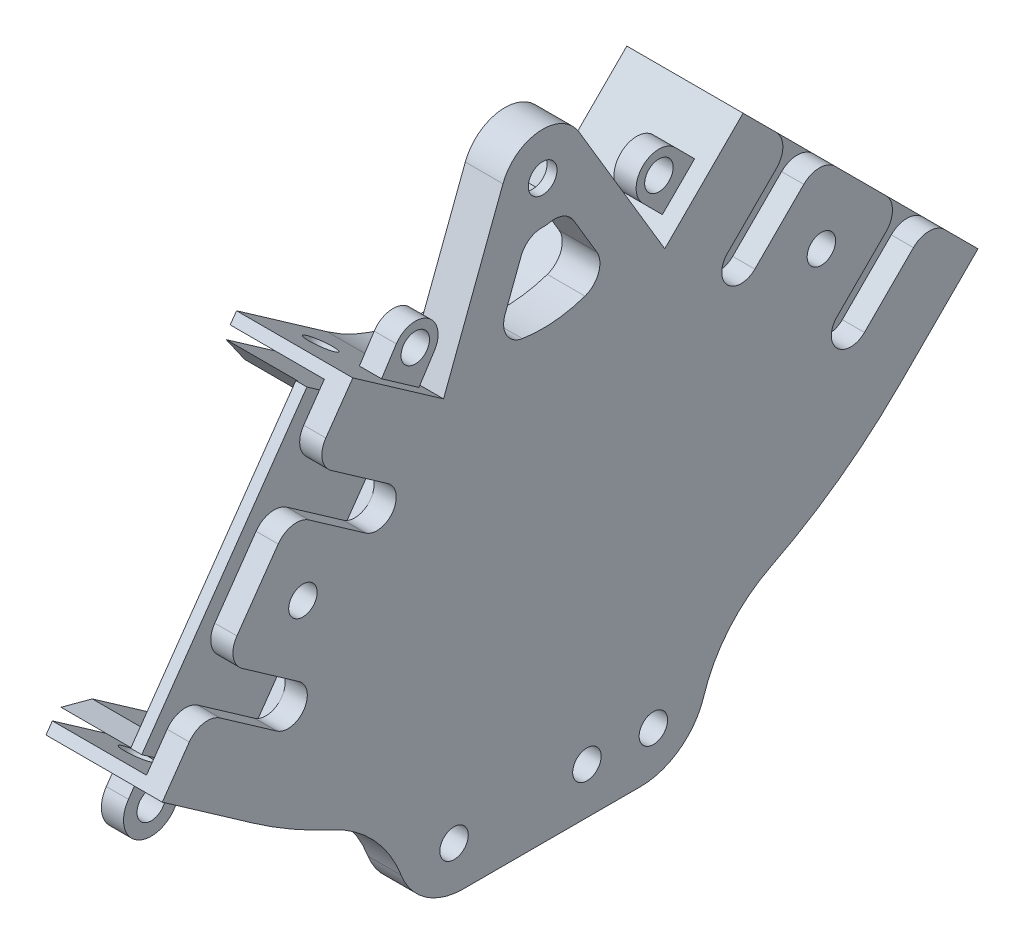
SolidWorks part; units mm, degrees
ref_plane "Front Plane" through (0, 0, 0) normal (0, 0, 1) x (1, 0, 0)
ref_plane "Top Plane" through (0, 0, 0) normal (0, 1, 0) x (1, 0, 0)
ref_plane "Right Plane" through (0, 0, 0) normal (1, 0, 0) x (0, 0, -1)
sketch "Sketch3" plane through (0, 0, 0) normal (1, 0, 0) x (0, 0, -1)
  line L0 (-22.7274, -32.4581) -> (-62.0633, -88.6355)
  line L1 (28.0184, -28.0184) -> (76.5118, -76.5118)
  line L2 (-22.7274, -32.4581) -> (0, 0) construction
  line L3 (0, 0) -> (28.0184, -28.0184) construction
  line L4 (0, 40.513) -> (0, -40.513) construction
  line L5 (-62.0633, -88.6355) -> (-66.4339, -94.8775)
  line L6 (76.5118, -76.5118) -> (81.8999, -81.8999)
  arc A2 (-62.0633, -88.6355) -> (76.5118, -76.5118) centre (0, 0) ccw
  arc A4 (-27.098, -38.7) -> (33.4066, -33.4066) centre (0, 0) ccw
  arc A5 (-22.7274, -32.4581) -> (28.0184, -28.0184) centre (0, 0) ccw
  arc A6 (-66.4339, -94.8775) -> (81.8999, -81.8999) centre (0, 0) ccw
  dimension "D1" = 216.408
  dimension "D2" = 135
  dimension "D3" = 94.488
  dimension "D4" = 7.62
  dimension "D6" = 7.62
  dimension "D5" = 80
extrude "Base extrude" add sketch "Sketch3" along normal blind 58.42 contours L5 A6 L6 A2 | A5 L0 A4 L1 region at (0, -39.9408, -3.4944) region at (0, -109.321, -9.5643)
sketch "Sketch4" plane through (58.42, 0, 0) normal (1, 0, 0) x (0, 0, -1)
  line L0 (-66.4339, -94.8775) -> (-22.7274, -32.4581)
  line L1 (28.0184, -28.0184) -> (81.8999, -81.8999)
  arc A0 (-22.7274, -32.4581) -> (28.0184, -28.0184) centre (0, 0) ccw
  arc A1 (-22.7274, -32.4581) -> (28.0184, -28.0184) centre (0, 0) ccw construction
  arc A2 (-66.4339, -94.8775) -> (81.8999, -81.8999) centre (0, 0) ccw
  arc A3 (-66.4339, -94.8775) -> (81.8999, -81.8999) centre (0, 0) ccw construction
  arc M1 (28.0184, -28.0184) -> (-22.7274, -32.4581) centre (0, 0) cw
  line M2 (-22.7274, -32.4581) -> (-27.098, -38.7)
  arc M3 (-27.098, -38.7) -> (33.4066, -33.4066) centre (0, 0) ccw
  line M4 (33.4066, -33.4066) -> (28.0184, -28.0184)
extrude "Outer wall" add sketch "Sketch4" along normal blind 7.62 contours L0 A2 L1 M3 | M4 M1 M2 M3 region at (58.42, -79.1939, -6.9286) region at (58.42, -39.9408, -3.4944)
ref_plane "Midplane" through (29.21, 0, 0) normal (-1, 0, 0) x (0, 0, 1)
mirror "Mirror1" about plane through (29.21, 0, 0) normal (-1, 0, 0) of "Outer wall"
sketch "Sketch6" plane through (0, 0, 0) normal (0, 0.5736, 0.8192) x (1, 0, 0)
  line L27 (-5.08, -42.164) -> (63.5, -42.164)
  line L28 (-5.08, -42.164) -> (-5.08, -113.284)
  line L29 (-5.08, -113.284) -> (63.5, -113.284)
  line L30 (63.5, -42.164) -> (63.5, -113.284)
  line L31 (-2.54, -44.704) -> (60.96, -44.704)
  line L32 (-2.54, -44.704) -> (-2.54, -110.744)
  line L33 (-2.54, -110.744) -> (60.96, -110.744)
  line L34 (60.96, -44.704) -> (60.96, -110.744)
  line L35 (58.42, -47.244) -> (0, -47.244) construction
  line L36 (0, -108.204) -> (0, -18.7894) construction
  line L37 (58.42, -18.7894) -> (58.42, -108.204) construction
  line L38 (58.42, -108.204) -> (0, -108.204) construction
  line L40 (0, -47.244) -> (58.42, -47.244)
  line L41 (0, -47.244) -> (0, -108.204)
  line L42 (0, -108.204) -> (58.42, -108.204)
  line L43 (58.42, -47.244) -> (58.42, -108.204)
  line L44 (-7.62, -39.624) -> (66.04, -39.624)
  line L45 (-7.62, -39.624) -> (-7.62, -115.824)
  line L46 (-7.62, -115.824) -> (66.04, -115.824)
  line L47 (66.04, -39.624) -> (66.04, -115.824)
  line M21 (-7.62, -39.624) -> (-7.62, -115.824)
  line M22 (-7.62, -115.824) -> (66.04, -115.824)
  line M23 (66.04, -115.824) -> (66.04, -39.624)
  line M24 (66.04, -39.624) -> (-7.62, -39.624)
  line M25 (58.42, -108.204) -> (0, -108.204)
  line M26 (0, -108.204) -> (0, -47.244)
  line M27 (0, -47.244) -> (58.42, -47.244)
  line M28 (58.42, -47.244) -> (58.42, -108.204)
  dimension "D1" = 2.54
  dimension "D2" = 2.54
  dimension "D3" = 2.54
  dimension "D4" = 2.54
  dimension "D5" = 2.54
  dimension "D6" = 2.54
  dimension "D7" = 2.54
  dimension "D8" = 2.54
extrude "Endcap 1" add sketch "Sketch6" along normal blind 25.4 contours L27 L30 L29 L28 M24 M21 M22 M23 | L34 L31 L32 L33 M28 M25 M26 M27 region at (29.21, -37.3698, 26.1667) region at (29.21, -33.3262, 23.3353)
sketch "Sketch7" plane through (0, 0, 0) normal (0, 0.7071, -0.7071) x (1, 0, 0)
  line L0 (-5.08, 113.284) -> (63.5, 113.284)
  line L1 (-5.08, 113.284) -> (-5.08, 42.164)
  line L2 (-5.08, 42.164) -> (63.5, 42.164)
  line L3 (63.5, 113.284) -> (63.5, 42.164)
  line L4 (-2.54, 110.744) -> (60.96, 110.744)
  line L5 (-2.54, 110.744) -> (-2.54, 44.704)
  line L6 (-2.54, 44.704) -> (60.96, 44.704)
  line L7 (60.96, 110.744) -> (60.96, 44.704)
  line L8 (0, 108.204) -> (58.42, 108.204)
  line L9 (0, 108.204) -> (0, 47.244)
  line L10 (0, 47.244) -> (58.42, 47.244)
  line L11 (58.42, 108.204) -> (58.42, 47.244)
  line L12 (-7.62, 115.824) -> (66.04, 115.824)
  line L13 (-7.62, 115.824) -> (-7.62, 39.624)
  line L14 (-7.62, 39.624) -> (66.04, 39.624)
  line L15 (66.04, 115.824) -> (66.04, 39.624)
  line L16 (58.42, 108.204) -> (0, 108.204) construction
  line L17 (58.42, 47.244) -> (58.42, 108.204) construction
  line L18 (66.04, 115.824) -> (-7.62, 115.824) construction
  line L19 (66.04, 39.624) -> (66.04, 115.824) construction
  line L20 (-7.62, 39.624) -> (-7.62, 115.824) construction
  line L21 (66.04, 39.624) -> (-7.62, 39.624) construction
  line M17 (66.04, 115.824) -> (-7.62, 115.824)
  line M18 (-7.62, 115.824) -> (-7.62, 39.624)
  line M19 (-7.62, 39.624) -> (66.04, 39.624)
  line M20 (66.04, 39.624) -> (66.04, 115.824)
  line M21 (0, 47.244) -> (0, 108.204)
  line M22 (0, 108.204) -> (58.42, 108.204)
  line M23 (58.42, 108.204) -> (58.42, 47.244)
  line M24 (58.42, 47.244) -> (0, 47.244)
  dimension "D1" = 2.54
  dimension "D2" = 2.54
  dimension "D3" = 2.54
  dimension "D4" = 2.54
  dimension "D5" = 2.54
  dimension "D6" = 2.54
  dimension "D7" = 2.54
  dimension "D8" = 2.54
extrude "Endcap 2" add sketch "Sketch7" along normal blind 25.4 contours L0 L3 L2 L1 M20 M17 M18 M19 | L7 L4 L5 L6 M24 M21 M22 M23 region at (29.21, -77.66, -77.66) region at (29.21, -81.1505, -81.1505)
chamfer "Internal Chamfer" distance 7.62 angle 20 4 edges at (29.21, -74.0667, 82.8697) (29.21, -24.1312, 47.9045) (29.21, -58.5513, -94.4723) (29.21, -15.446, -51.3671) first distance on face at (29.21, -81.3511, 72.4665) first distance on face at (29.21, -31.4156, 37.5013) first distance on face at (29.21, -67.5315, -85.492) first distance on face at (29.21, -24.4263, -42.3868)
ref_plane "Plane2" through (0, -13.9736, -1.2225) normal (0, -0.9962, -0.0872) x (-1, 0, 0)
sketch "Sketch10" plane through (0, -13.9736, -1.2225) normal (0, -0.9962, -0.0872) x (-1, 0, 0)
  line L0 (-66.04, 93.9078) -> (7.62, 93.9078) construction
  line L1 (-16.51, 95.5358) -> (-41.91, 95.5358)
  line L2 (-16.51, 95.5358) -> (-16.51, -82.1857)
  line L3 (-16.51, -82.1857) -> (-41.91, -82.1857)
  line L4 (-41.91, 95.5358) -> (-41.91, -82.1857)
  point P4 (-29.21, 93.9078)
  point P5 (-29.21, 95.5358)
  dimension "D1" = 25.4
extrude "Flywheel Hole" cut sketch "Sketch10" along normal up to next
sketch "Sketch11" plane through (-7.62, 0, 0) normal (-1, 0, 0) x (0, 0, 1)
  line L0 (-25.2982, 2.2719) -> (-28.0184, -28.0184)
  line L4 (-3.0636, -22.3183) -> (-4.5937, -39.3568)
  line L5 (6.8995, -21.445) -> (11.3704, -37.9575)
  line L6 (-20.4217, -1.79) -> (20.4217, 1.79) construction
  line L7 (24.5172, 6.6383) -> (33.1306, -25.1737)
  line L8 (43.5339, -17.8892) -> (22.7274, -32.4581) construction
  line L10 (1.5525, -17.7121) -> (-2.2178, 25.303) construction
  line L11 (22.7274, -32.4581) -> (43.5339, -17.8892)
  line L12 (22.7274, -32.4581) -> (33.1306, -25.1737)
  arc A1 (-28.0184, -28.0184) -> (22.7274, -32.4581) centre (0, 0) ccw construction
  circle A3 centre (0, 0) radius 4.064
  arc A4 (24.5172, 6.6383) -> (-25.2982, 2.2719) centre (0, 0) ccw
  circle A6 centre (-20.4217, -1.79) radius 2.5
  circle A7 centre (20.4217, 1.79) radius 2.5
  arc A8 (-3.0636, -22.3183) -> (6.8995, -21.445) centre (1.9961, -22.7727) cw
  arc A11 (11.3704, -37.9575) -> (22.7274, -32.4581) centre (0, 0) ccw
  arc A12 (-28.0184, -28.0184) -> (22.7274, -32.4581) centre (0, 0) ccw
  arc A13 (-28.0184, -28.0184) -> (-4.5937, -39.3568) centre (0, 0) ccw
  point P22 (0, 0)
  dimension "D3" = 8.128
  dimension "D2" = 25.4
  dimension "D1" = 5
  dimension "D5" = 5.08
  dimension "D4" = 41
  dimension "D7" = 43.18
  dimension "D6" = 0
extrude "Flywheel holder" add sketch "Sketch11" against normal blind 7.62
sketch "Sketch12" plane through (-7.62, 0, 0) normal (-1, 0, 0) x (0, 0, 1)
  circle A0 centre (0, 0) radius 14.605
  dimension "D1" = 29.21
extrude "Motor insert" cut sketch "Sketch12" against normal blind 6.35
sketch "Sketch14" plane through (-7.62, 0, 0) normal (-1, 0, 0) x (0, 0, 1)
  line L1 (-106.5763, 40.9543) -> (105.556, 40.9543)
  line L2 (-106.5763, 40.9543) -> (-106.5763, -120.0185)
  line L3 (-106.5763, -120.0185) -> (105.556, -120.0185)
  line L4 (105.556, 40.9543) -> (105.556, -120.0185)
extrude "Cut-Extrude2" cut sketch "Sketch14" against normal up to surface (49.53 mm away) up to face at (41.91, -26.9401, -2.3569)
sketch "Sketch15" plane through (41.91, 0, 0) normal (-1, 0, 0) x (0, 0, 1)
  line L0 (-93.8083, -77.7308) -> (-89.6212, -74.1787)
  line L1 (-99.8604, -63.9394) -> (-81.8999, -81.8999) construction
  line L2 (-89.6212, -74.1787) -> (-80.6312, -83.1493)
  line L3 (-80.6312, -83.1493) -> (-85.0539, -86.9012)
  line L4 (-16.51, -121.4959) -> (-16.51, -114.6413)
  line L5 (-16.51, -114.6413) -> (-3.8593, -115.7597)
  line L6 (-3.8593, -115.7597) -> (-3.8593, -120.7059)
  line L7 (63.1155, -104.8839) -> (59.3284, -99.4753)
  line L8 (59.3284, -99.4753) -> (69.9059, -92.4464)
  line L9 (66.4339, -94.8775) -> (87.2404, -80.3086) construction
  line L10 (69.9059, -92.4464) -> (73.4123, -97.454)
  circle A0 centre (-89.7004, -82.5731) radius 3.2639
  circle A1 centre (-10.16, -121.4959) radius 3.2639
  circle A2 centre (68.1904, -101.0671) radius 3.2639
  arc A3 (-93.8083, -77.7308) -> (-85.0539, -86.9012) centre (-89.7004, -82.5731) ccw
  arc A5 (62.868, -104.5305) -> (73.3715, -97.3959) centre (68.1904, -101.0671) ccw
  arc A6 (-81.8999, -81.8999) -> (66.4339, -94.8775) centre (0, 0) ccw construction
  arc A7 (-16.51, -121.4959) -> (-3.8593, -120.7059) centre (-10.16, -121.4959) ccw
  line M28 (-99.8604, -63.9394) -> (-81.8999, -81.8999)
  arc M29 (-81.8999, -81.8999) -> (66.4339, -94.8775) centre (0, 0) ccw
  line M30 (66.4339, -94.8775) -> (87.2404, -80.3086)
  dimension "D4" = 6.5278
  dimension "D5" = 12.7
  dimension "D1" = 121.92
  dimension "D2" = 121.92
  dimension "D3" = 121.92
  dimension "D6" = 10.16
  dimension "D7" = 10.16
  dimension "D8" = 19.05
  dimension "D9" = 12.7
  dimension "D10" = 12.7
  dimension "D11" = 12.7
extrude "Joining screw holes" add sketch "Sketch15" against normal blind 5.08 contours L0 A3 L3 A0 M29 M28 | L4 A7 L6 A1 M29 | L7 A5 L10 A2 M30 M29 region at (41.91, -97.4205, 63.0391) region at (41.91, -115.5565, -10.2161) region at (41.91, -76.1174, -91.5767)
ref_plane "Plane3" through (59.69, 0, 0) normal (1, 0, 0) x (0, 0, -1)
sketch "Sketch16" plane through (59.69, 0, 0) normal (1, 0, 0) x (0, 0, -1)
  line L0 (-43.5339, -17.8892) -> (-22.7274, -32.4581) construction
  line L1 (45.9789, -10.0579) -> (28.0184, -28.0184) construction
  line L2 (-29.7459, -19.9251) -> (-33.1306, -25.1737)
  line L3 (-33.1306, -25.1737) -> (-24.5641, -31.172)
  line L4 (-24.5641, -31.172) -> (-21.1794, -25.9235)
  line L5 (26.7818, -20.2747) -> (31.2719, -24.7649)
  line L6 (31.2719, -24.7649) -> (38.6683, -17.3685)
  line L7 (38.6683, -17.3685) -> (34.1782, -12.8783)
  line L8 (34.1782, -12.8783) -> (26.7818, -20.2747) construction
  circle A0 centre (-25.4, -22.8348) radius 3.2639
  circle A1 centre (30.48, -16.5765) radius 3.2639
  arc A2 (-21.1794, -25.9235) -> (-29.8435, -20.0764) centre (-25.4, -22.8348) ccw
  arc A3 (34.1782, -12.8783) -> (26.7818, -20.2747) centre (30.48, -16.5765) ccw
  dimension "D3" = 6.5278
  dimension "D1" = 6.35
  dimension "D2" = 6.35
  dimension "D4" = 25.4
  dimension "D5" = 30.48
  dimension "D6" = 55.88
  dimension "D7" = 6.2582
extrude "Flywheel cover connectors" add sketch "Sketch16" along normal blind 5.08 contours L4 A2 L2 L3 A0 | L7 L8 A1 L5 L6 | L8 A3 A1 region at (59.69, -18.7043, 22.5078) region at (59.69, -19.2478, -33.1513) region at (59.69, -12.9676, -26.8711)
sketch "Sketch17" plane through (66.04, 0, 0) normal (1, 0, 0) x (0, 0, -1)
  line L0 (-30.48, -111.7415) -> (-30.48, -132.08)
  line L1 (-30.48, -132.08) -> (35.56, -132.08)
  line L2 (35.56, -132.08) -> (35.56, -110.2301)
  circle A0 centre (-20.32, -121.92) radius 3.2639
  circle A1 centre (25.4, -121.92) radius 3.2639
  arc A2 (-66.4339, -94.8775) -> (81.8999, -81.8999) centre (0, 0) ccw construction
  circle A4 centre (10.16, -121.4959) radius 3.2639
  arc A5 (-66.4339, -94.8775) -> (81.8999, -81.8999) centre (0, 0) ccw
  arc A6 (-30.48, -111.7415) -> (35.56, -110.2301) centre (0, 0) ccw
  circle A7 centre (10.16, -121.4959) radius 3.2639 construction
  dimension "D1" = 6.5278
  dimension "D2" = 20.32
  dimension "D3" = 25.4
  dimension "D4" = 121.92
  dimension "D5" = 0
  dimension "D6" = 10.16
  dimension "D7" = 10.16
  dimension "D8" = 10.16
extrude "80-20 connector" add sketch "Sketch17" against normal blind 5.08
fillet "Fillet1" radius 30.48 2 edges at (63.5, -111.7415, 30.48) (63.5, -110.2301, -35.56)
fillet "Fillet2" radius 15.24 2 edges at (63.5, -132.08, -35.56) (63.5, -132.08, 30.48)
sketch "Sketch18" plane through (66.04, 0, 0) normal (1, 0, 0) x (0, 0, -1)
  line L0 (-35.474, -42.9126) -> (-52.6394, -30.8933)
  line L1 (-87.2404, -80.3086) -> (-43.5339, -17.8892) construction
  line L2 (-52.6394, -30.8933) -> (-57.7385, -38.1755)
  line L3 (-57.7385, -38.1755) -> (-40.5731, -50.1948)
  line L4 (-55.8704, -72.0416) -> (-73.0358, -60.0223)
  line L5 (-73.0358, -60.0223) -> (-78.1349, -67.3046)
  line L6 (-78.1349, -67.3046) -> (-60.9695, -79.3239)
  line L7 (42.3868, -36.1006) -> (57.2042, -21.2832)
  line L8 (45.9789, -10.0579) -> (99.8604, -63.9394) construction
  line L9 (57.2042, -21.2832) -> (63.4904, -27.5694)
  line L10 (63.4904, -27.5694) -> (48.673, -42.3868)
  line L11 (67.5315, -61.2453) -> (82.3489, -46.4279)
  line L12 (82.3489, -46.4279) -> (88.6351, -52.7141)
  line L13 (88.6351, -52.7141) -> (73.8177, -67.5315)
  line L14 (-43.5339, -17.8892) -> (-22.7274, -32.4581) construction
  line L15 (45.9789, -10.0579) -> (28.0184, -28.0184) construction
  line L16 (99.8604, -63.9394) -> (81.8999, -81.8999) construction
  line L17 (-87.2404, -80.3086) -> (-66.4339, -94.8775) construction
  line L18 (-24.1843, -34.5387) -> (-64.977, -92.7968) construction
  arc A0 (-40.5731, -50.1948) -> (-35.474, -42.9126) centre (-38.0236, -46.5537) ccw
  arc A1 (-60.9695, -79.3239) -> (-55.8704, -72.0416) centre (-58.42, -75.6827) ccw
  arc A2 (42.3868, -36.1006) -> (48.673, -42.3868) centre (45.5299, -39.2437) ccw
  arc A3 (67.5315, -61.2453) -> (73.8177, -67.5315) centre (70.6746, -64.3884) ccw
  dimension "D1" = 8.89
  dimension "D3" = 20.32
  dimension "D4" = 20.32
  dimension "D5" = 20.32
  dimension "D6" = 20.32
extrude "Support Removal" cut sketch "Sketch18" against normal up to next
fillet "Fillet3" radius 5.08 8 edges at (64.77, -52.7141, -88.6351) (64.77, -46.4279, -82.3489) (64.77, -27.5694, -63.4904) (64.77, -21.2832, -57.2042) (64.77, -67.3046, 78.1349) (64.77, -60.0223, 73.0358) (64.77, -38.1755, 57.7385) (64.77, -30.8933, 52.6394)
sketch "Sketch19" plane through (66.04, 0, 0) normal (1, 0, 0) x (0, 0, -1)
  line L0 (-70.122, -55.861) -> (-60.6522, -42.3368) construction
  line L1 (67.0825, -31.1615) -> (78.7568, -42.8358) construction
  line L2 (-65.3871, -49.0989) -> (-54.9839, -56.3834) construction
  line L3 (-34.3825, -49.1033) -> (-54.7788, -78.2323) construction
  line L4 (67.5315, -67.5315) -> (42.3868, -42.3868) construction
  line L5 (72.9197, -36.9987) -> (63.9394, -45.9789) construction
  circle A0 centre (-54.9839, -56.3834) radius 3.2639
  circle A1 centre (63.9394, -45.9789) radius 3.2639
  point P4 (-65.3871, -49.0989)
  point P5 (72.9197, -36.9987)
  dimension "D1" = 6.5278
  dimension "D2" = 12.7
  dimension "D3" = 12.7
extrude "Cut-Extrude3" cut sketch "Sketch19" against normal up to next contours A1 | A0 region at (66.04, -56.3834, 54.9839) region at (66.04, -45.9789, -63.9394)
sketch "Sketch20" plane through (0, -94.8775, 66.4339) normal (0, -0.8192, 0.5736) x (1, 0, 0)
  line L0 (63.5, 25.4) -> (63.5, 0) construction
  line L1 (41.91, 0) -> (63.5, 0) construction
  circle A0 centre (50.8, 12.7) radius 3.2639
  dimension "D1" = 6.5278
  dimension "D2" = 12.7
  dimension "D3" = 12.7
extrude "Cut-Extrude4" cut sketch "Sketch20" against normal up to next
ref_plane "Plane4" through (0, -63.6678, 44.5807) normal (0, 0.8192, -0.5736) x (1, 0, 0)
mirror "Mirror2" about plane through (0, -63.6678, 44.5807) normal (0, 0.8192, -0.5736) of "Cut-Extrude4"
sketch "Sketch21" plane through (0, -81.8999, -81.8999) normal (0, -0.7071, -0.7071) x (1, 0, 0)
  line L0 (66.04, 0) -> (46.99, 0) construction
  line L1 (63.5, -25.4) -> (63.5, 0) construction
  circle A0 centre (50.8, -12.7) radius 3.2639
  dimension "D1" = 6.5278
  dimension "D2" = 12.7
  dimension "D3" = 12.7
extrude "Cut-Extrude5" cut sketch "Sketch21" against normal up to next contours A0
sketch "Sketch22" plane through (66.04, 0, 0) normal (1, 0, 0) x (0, 0, -1)
  line L38 (99.8604, -63.9394) -> (92.2272, -56.3062)
  line L39 (85.043, -56.3062) -> (73.8177, -67.5315)
  line L40 (67.5315, -61.2453) -> (78.7568, -50.02)
  line L41 (78.7568, -42.8358) -> (67.0825, -31.1615)
  line L42 (59.8983, -31.1615) -> (48.673, -42.3868)
  line L43 (42.3868, -36.1006) -> (53.6121, -24.8753)
  line L44 (53.6121, -17.6911) -> (45.9789, -10.0579)
  line L45 (45.9789, -10.0579) -> (28.0184, -28.0184)
  line L46 (-22.7274, -32.4581) -> (-43.5339, -17.8892)
  line L47 (-43.5339, -17.8892) -> (-49.7256, -26.732)
  line L48 (-48.4781, -33.807) -> (-35.474, -42.9126)
  line L49 (-40.5731, -50.1948) -> (-53.5772, -41.0893)
  line L50 (-60.6522, -42.3368) -> (-70.122, -55.861)
  line L51 (-68.8745, -62.9361) -> (-55.8704, -72.0416)
  line L52 (-60.9695, -79.3239) -> (-73.9736, -70.2184)
  line L53 (-81.0486, -71.4659) -> (-87.2404, -80.3086)
  line L54 (-87.2404, -80.3086) -> (-66.4339, -94.8775)
  line L55 (-18.1792, -132.08) -> (22.4243, -132.08)
  line L56 (81.8999, -81.8999) -> (99.8604, -63.9394)
  line L57 (99.8604, -63.9394) -> (92.2272, -56.3062)
  line L58 (85.043, -56.3062) -> (73.8177, -67.5315)
  line L59 (67.5315, -61.2453) -> (78.7568, -50.02)
  line L60 (78.7568, -42.8358) -> (67.0825, -31.1615)
  line L61 (59.8983, -31.1615) -> (48.673, -42.3868)
  line L62 (42.3868, -36.1006) -> (53.6121, -24.8753)
  line L63 (53.6121, -17.6911) -> (45.9789, -10.0579)
  line L64 (45.9789, -10.0579) -> (28.0184, -28.0184)
  line L65 (-22.7274, -32.4581) -> (-43.5339, -17.8892)
  line L66 (-43.5339, -17.8892) -> (-49.7256, -26.732)
  line L67 (-48.4781, -33.807) -> (-35.474, -42.9126)
  line L68 (-40.5731, -50.1948) -> (-53.5772, -41.0893)
  line L69 (-60.6522, -42.3368) -> (-70.122, -55.861)
  line L70 (-68.8745, -62.9361) -> (-55.8704, -72.0416)
  line L71 (-60.9695, -79.3239) -> (-73.9736, -70.2184)
  line L72 (-81.0486, -71.4659) -> (-87.2404, -80.3086)
  line L73 (-87.2404, -80.3086) -> (-66.4339, -94.8775)
  line L74 (-18.1792, -132.08) -> (22.4243, -132.08)
  line L75 (81.8999, -81.8999) -> (99.8604, -63.9394)
  circle A21 centre (-54.9839, -56.3834) radius 3.2639
  circle A22 centre (-54.9839, -56.3834) radius 3.2639
  circle A24 centre (-20.32, -121.92) radius 3.2639
  circle A25 centre (-20.32, -121.92) radius 3.2639
  circle A27 centre (10.16, -121.4959) radius 3.2639
  circle A28 centre (10.16, -121.4959) radius 3.2639
  circle A30 centre (25.4, -121.92) radius 3.2639
  circle A31 centre (25.4, -121.92) radius 3.2639
  circle A33 centre (63.9394, -45.9789) radius 3.2639
  circle A34 centre (63.9394, -45.9789) radius 3.2639
  arc A38 (92.2272, -56.3062) -> (85.043, -56.3062) centre (88.6351, -59.8983) ccw
  arc A39 (67.5315, -61.2453) -> (73.8177, -67.5315) centre (70.6746, -64.3884) ccw
  arc A40 (78.7568, -50.02) -> (78.7568, -42.8358) centre (75.1647, -46.4279) ccw
  arc A41 (67.0825, -31.1615) -> (59.8983, -31.1615) centre (63.4904, -34.7536) ccw
  arc A42 (42.3868, -36.1006) -> (48.673, -42.3868) centre (45.5299, -39.2437) ccw
  arc A43 (53.6121, -24.8753) -> (53.6121, -17.6911) centre (50.02, -21.2832) ccw
  arc A44 (-22.7274, -32.4581) -> (28.0184, -28.0184) centre (0, 0) ccw
  arc A45 (-49.7256, -26.732) -> (-48.4781, -33.807) centre (-45.5643, -29.6458) ccw
  arc A46 (-40.5731, -50.1948) -> (-35.474, -42.9126) centre (-38.0236, -46.5537) ccw
  arc A47 (-53.5772, -41.0893) -> (-60.6522, -42.3368) centre (-56.491, -45.2506) ccw
  arc A48 (-70.122, -55.861) -> (-68.8745, -62.9361) centre (-65.9607, -58.7748) ccw
  arc A49 (-60.9695, -79.3239) -> (-55.8704, -72.0416) centre (-58.42, -75.6827) ccw
  arc A50 (-73.9736, -70.2184) -> (-81.0486, -71.4659) centre (-76.8873, -74.3796) ccw
  arc A51 (-66.4339, -94.8775) -> (-48.2489, -105.296) centre (0, 0) ccw
  arc A52 (-32.4348, -122.2285) -> (-48.2489, -105.296) centre (-60.9459, -133.0055) ccw
  arc A53 (-32.4348, -122.2285) -> (-18.1792, -132.08) centre (-18.1792, -116.84) ccw
  arc A54 (22.4243, -132.08) -> (36.9629, -121.4104) centre (22.4243, -116.84) ccw
  arc A55 (52.2817, -103.3529) -> (36.9629, -121.4104) centre (66.04, -130.5511) ccw
  arc A56 (52.2817, -103.3529) -> (81.8999, -81.8999) centre (0, 0) ccw
  arc A57 (92.2272, -56.3062) -> (85.043, -56.3062) centre (88.6351, -59.8983) ccw
  arc A58 (67.5315, -61.2453) -> (73.8177, -67.5315) centre (70.6746, -64.3884) ccw
  arc A59 (78.7568, -50.02) -> (78.7568, -42.8358) centre (75.1647, -46.4279) ccw
  arc A60 (67.0825, -31.1615) -> (59.8983, -31.1615) centre (63.4904, -34.7536) ccw
  arc A61 (42.3868, -36.1006) -> (48.673, -42.3868) centre (45.5299, -39.2437) ccw
  arc A62 (53.6121, -24.8753) -> (53.6121, -17.6911) centre (50.02, -21.2832) ccw
  arc A63 (-22.7274, -32.4581) -> (28.0184, -28.0184) centre (0, 0) ccw
  arc A64 (-49.7256, -26.732) -> (-48.4781, -33.807) centre (-45.5643, -29.6458) ccw
  arc A65 (-40.5731, -50.1948) -> (-35.474, -42.9126) centre (-38.0236, -46.5537) ccw
  arc A66 (-53.5772, -41.0893) -> (-60.6522, -42.3368) centre (-56.491, -45.2506) ccw
  arc A67 (-70.122, -55.861) -> (-68.8745, -62.9361) centre (-65.9607, -58.7748) ccw
  arc A68 (-60.9695, -79.3239) -> (-55.8704, -72.0416) centre (-58.42, -75.6827) ccw
  arc A69 (-73.9736, -70.2184) -> (-81.0486, -71.4659) centre (-76.8873, -74.3796) ccw
  arc A70 (-66.4339, -94.8775) -> (-48.2489, -105.296) centre (0, 0) ccw
  arc A71 (-32.4348, -122.2285) -> (-48.2489, -105.296) centre (-60.9459, -133.0055) ccw
  arc A72 (-32.4348, -122.2285) -> (-18.1792, -132.08) centre (-18.1792, -116.84) ccw
  arc A73 (22.4243, -132.08) -> (36.9629, -121.4104) centre (22.4243, -116.84) ccw
  arc A74 (52.2817, -103.3529) -> (36.9629, -121.4104) centre (66.04, -130.5511) ccw
  arc A75 (52.2817, -103.3529) -> (81.8999, -81.8999) centre (0, 0) ccw
  circle M44 centre (63.9394, -45.9789) radius 3.2639
  circle M45 centre (-54.9839, -56.3834) radius 3.2639
  line M46 (99.8604, -63.9394) -> (92.2272, -56.3062)
  arc M47 (92.2272, -56.3062) -> (85.043, -56.3062) centre (88.6351, -59.8983) ccw
  line M48 (85.043, -56.3062) -> (73.8177, -67.5315)
  arc M49 (73.8177, -67.5315) -> (67.5315, -61.2453) centre (70.6746, -64.3884) cw
  line M50 (67.5315, -61.2453) -> (78.7568, -50.02)
  arc M51 (78.7568, -50.02) -> (78.7568, -42.8358) centre (75.1647, -46.4279) ccw
  line M52 (78.7568, -42.8358) -> (67.0825, -31.1615)
  arc M53 (67.0825, -31.1615) -> (59.8983, -31.1615) centre (63.4904, -34.7536) ccw
  line M54 (59.8983, -31.1615) -> (48.673, -42.3868)
  arc M55 (48.673, -42.3868) -> (42.3868, -36.1006) centre (45.5299, -39.2437) cw
  line M56 (42.3868, -36.1006) -> (53.6121, -24.8753)
  arc M57 (53.6121, -24.8753) -> (53.6121, -17.6911) centre (50.02, -21.2832) ccw
  line M58 (53.6121, -17.6911) -> (45.9789, -10.0579)
  line M59 (45.9789, -10.0579) -> (28.0184, -28.0184)
  arc M60 (28.0184, -28.0184) -> (-22.7274, -32.4581) centre (0, 0) cw
  line M61 (-22.7274, -32.4581) -> (-43.5339, -17.8892)
  line M62 (-43.5339, -17.8892) -> (-49.7256, -26.732)
  arc M63 (-49.7256, -26.732) -> (-48.4781, -33.807) centre (-45.5643, -29.6458) ccw
  line M64 (-48.4781, -33.807) -> (-35.474, -42.9126)
  arc M65 (-35.474, -42.9126) -> (-40.5731, -50.1948) centre (-38.0236, -46.5537) cw
  line M66 (-40.5731, -50.1948) -> (-53.5772, -41.0893)
  arc M67 (-53.5772, -41.0893) -> (-60.6522, -42.3368) centre (-56.491, -45.2506) ccw
  line M68 (-60.6522, -42.3368) -> (-70.122, -55.861)
  arc M69 (-70.122, -55.861) -> (-68.8745, -62.9361) centre (-65.9607, -58.7748) ccw
  line M70 (-68.8745, -62.9361) -> (-55.8704, -72.0416)
  arc M71 (-55.8704, -72.0416) -> (-60.9695, -79.3239) centre (-58.42, -75.6827) cw
  line M72 (-60.9695, -79.3239) -> (-73.9736, -70.2184)
  arc M73 (-73.9736, -70.2184) -> (-81.0486, -71.4659) centre (-76.8873, -74.3796) ccw
  line M74 (-81.0486, -71.4659) -> (-87.2404, -80.3086)
  line M75 (-87.2404, -80.3086) -> (-66.4339, -94.8775)
  arc M76 (-66.4339, -94.8775) -> (-48.2489, -105.296) centre (0, 0) ccw
  arc M77 (-48.2489, -105.296) -> (-32.4348, -122.2285) centre (-60.9459, -133.0055) cw
  arc M78 (-32.4348, -122.2285) -> (-18.1792, -132.08) centre (-18.1792, -116.84) ccw
  line M79 (-18.1792, -132.08) -> (22.4243, -132.08)
  arc M80 (22.4243, -132.08) -> (36.9629, -121.4104) centre (22.4243, -116.84) ccw
  arc M81 (36.9629, -121.4104) -> (52.2817, -103.3529) centre (66.04, -130.5511) cw
  arc M82 (52.2817, -103.3529) -> (81.8999, -81.8999) centre (0, 0) ccw
  line M83 (81.8999, -81.8999) -> (99.8604, -63.9394)
  circle M84 centre (10.16, -121.4959) radius 3.2639
  circle M85 centre (25.4, -121.92) radius 3.2639
  circle M86 centre (-20.32, -121.92) radius 3.2639
  dimension "D1" = 0
  dimension "D2" = 0
  dimension "D3" = 0
  dimension "D4" = 0
  dimension "D5" = 0
  dimension "D6" = 0
extrude "Thicken" add sketch "Sketch22" along normal blind 2.54 contours M83 M46 M47 M48 M49 M50 M51 M52 M53 M54 M55 M56 M57 M58 M59 M60 M61 M62 M63 M64 M65 M66 M67 M68 M69 M70 M71 M72 M73 M74 M75 M76 M77 M78 M79 M80 M81 M82 M45 M84 M86 M85 M44 region at (66.04, -75.2354, -5.8008)
sketch "Sketch23" plane through (68.58, 0, 0) normal (1, 0, 0) x (0, 0, -1)
  line L0 (-9.1013, 3.4534) -> (-22.7274, -32.4581)
  line L3 (8.3634, 4.9813) -> (28.0184, -28.0184)
  line L5 (-3.4534, -9.1013) -> (-10.6035, -27.9455)
  line L6 (28.0184, -28.0184) -> (45.9789, -10.0579)
  line L8 (15.2951, -25.6796) -> (15.2951, -25.6796)
  line L10 (0, 0) -> (-10.6035, -27.9455) construction
  line L11 (0, 0) -> (15.2951, -25.6796) construction
  line L12 (4.9813, -8.3634) -> (15.2951, -25.6796)
  line L19 (28.0184, -28.0184) -> (28.1487, -28.2372) construction
  line L20 (8.3634, 4.9813) -> (28.1487, -28.2372) construction
  circle A0 centre (0, 0) radius 3.302
  arc A1 (8.3634, 4.9813) -> (-9.1013, 3.4534) centre (0, 0) ccw
  arc A4 (-10.6035, -27.9455) -> (15.2951, -25.6796) centre (0, 0) ccw
  arc A5 (-22.7274, -32.4581) -> (28.0184, -28.0184) centre (0, 0) ccw
  arc A6 (-22.7274, -32.4581) -> (28.0184, -28.0184) centre (0, 0) ccw
  arc A7 (0, 0) -> (0, 0) centre (0, 0) ccw
  arc A8 (-3.4534, -9.1013) -> (4.9813, -8.3634) centre (0, 0) ccw
  arc A9 (8.3634, 4.9813) -> (-9.1013, 3.4534) centre (0, 0) ccw
  line M29 (45.9789, -10.0579) -> (28.0184, -28.0184)
  arc M30 (28.0184, -28.0184) -> (-22.7274, -32.4581) centre (0, 0) cw
  dimension "D2" = 0
extrude "Axle Holder" add sketch "Sketch23" against normal blind 8.636 contours A1 L0 A0 L5 A8 L12 A4 M30 M29 region at (68.58, 8.9922, 0.7867)
fillet "Fillet4" radius 5.08 4 edges at (64.262, -8.3634, -4.9813) (64.262, -9.1013, 3.4534) (64.262, -25.6796, -15.2951) (64.262, -27.9455, 10.6035)
sketch "Sketch24" plane through (59.944, 0, 0) normal (-1, 0, 0) x (0, 0, 1)
  line L6 (-3.4462, 5.969) -> (3.4462, 5.969)
  line L7 (3.4462, 5.969) -> (6.8924, 0)
  line L8 (6.8924, 0) -> (3.4462, -5.969)
  line L9 (3.4462, -5.969) -> (-3.4462, -5.969)
  line L10 (-3.4462, -5.969) -> (-6.8924, 0)
  line L11 (-6.8924, 0) -> (-3.4462, 5.969)
  line L12 (-3.4462, 5.969) -> (3.4462, -5.969) construction
  point P2 (0, 0)
  point P7 (0, 0)
  point P8 (-3.533, 6.1193)
  dimension "D1" = 120
  dimension "D2" = 11.938
extrude "Nut hole" cut sketch "Sketch24" against normal blind 6.35
